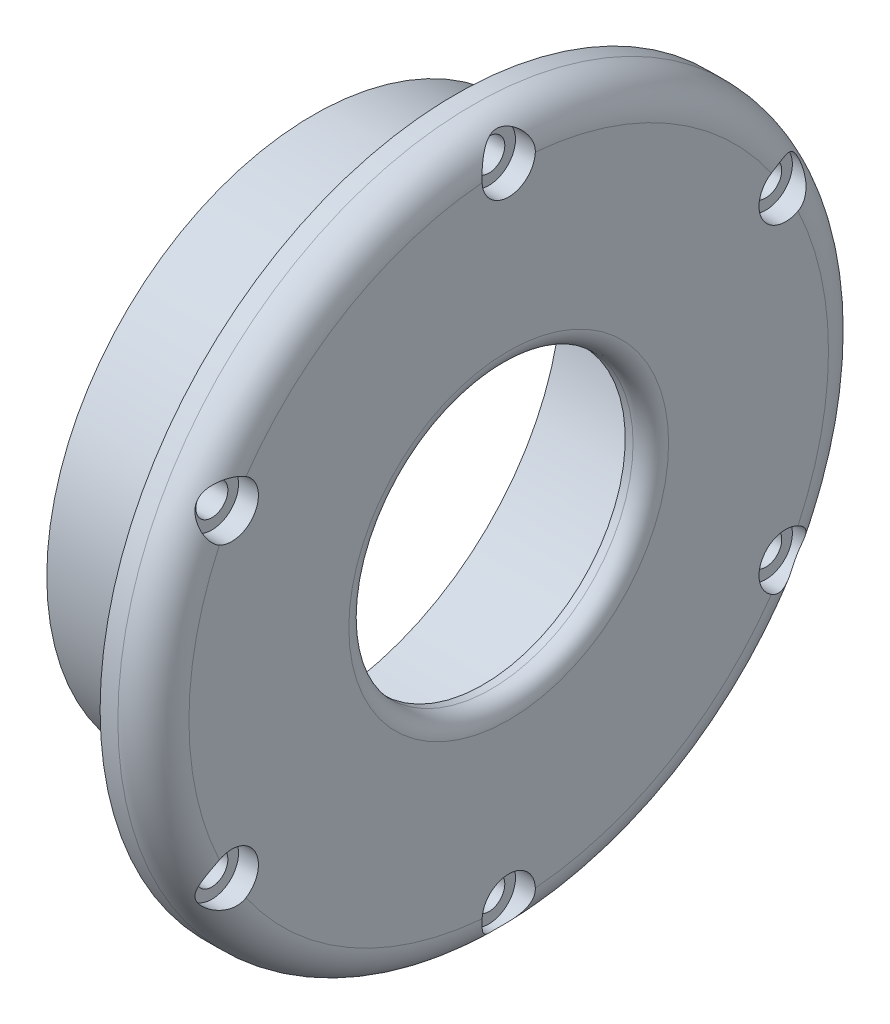
SolidWorks part; units mm, degrees
ref_plane "Front Plane" through (0, 0, 0) normal (0, 0, 1) x (1, 0, 0)
ref_plane "Top Plane" through (0, 0, 0) normal (0, 1, 0) x (1, 0, 0)
ref_plane "Right Plane" through (0, 0, 0) normal (1, 0, 0) x (0, 0, -1)
sketch "Sketch1" plane through (0, 0, 0) normal (0, 0, 1) x (1, 0, 0)
  line L0 (-15.2619, -32.7558) -> (53.5176, -32.7558)
  line L1 (22.9739, 67.2442) -> (37.9739, 67.2442)
  line L2 (-17.0261, 42.2442) -> (-17.0261, 37.2442)
  line L3 (30.7757, 7.2442) -> (37.9739, 7.2442)
  line L5 (37.9739, 67.2442) -> (37.9739, 7.2442)
  line L16 (-17.0261, 42.2442) -> (22.9739, 42.2442)
  line L17 (22.9739, 67.2442) -> (22.9739, 42.2442)
  line L20 (-17.0261, 37.2442) -> (17.9739, 37.2442)
  line L21 (17.9739, 31.2442) -> (17.9739, 37.2442)
  line L22 (17.9739, 31.2442) -> (22.9757, 31.2442)
  line L25 (30.7757, 22.2442) -> (30.7757, 7.2442)
  line L32 (30.7757, 22.2442) -> (22.9757, 22.2442)
  line L33 (22.9757, 31.2442) -> (22.9757, 22.2442)
  dimension "D1" = 60
  dimension "D2" = 40
  dimension "D3" = 40
  dimension "D4" = 35
  dimension "D5" = 6
  dimension "D6" = 5
  dimension "D7" = 15
  dimension "D8" = 7.1982
  dimension "D9" = 30
  dimension "D10" = 15
revolve "Revolve1" add sketch "Sketch1" angle 360 about L0 region at (25.1641, 40.2485, 0)
sketch "Sketch2" plane through (37.9739, 0, 0) normal (1, 0, 0) x (0, 0, -1)
  line L0 (0, -32.7558) -> (0, 57.2442)
  line L1 (0, -32.7558) -> (77.9423, 12.2442)
  line L2 (0, -32.7558) -> (77.9423, -77.7558)
  line L3 (0, -32.7558) -> (0, -122.7558)
  line L4 (0, -32.7558) -> (-77.9423, -77.7558)
  line L5 (0, -32.7558) -> (-77.9423, 12.2442)
  point P6 (0, 57.2442)
  point P9 (0, -32.7558)
  point P24 (-77.9423, 12.2442)
  point P27 (-77.9423, -77.7558)
  point P30 (0, -122.7558)
  point P33 (77.9423, -77.7558)
  point P36 (77.9423, 12.2442)
  dimension "D1" = 90
  dimension "D2" = 6
hole_wizard "CBORE for M8 Hex Socket Thin Head Cap Screw1" positions "Sketch2" profile "Sketch3" counterbore size "M8" standard "DIN"
sketch "Sketch3" plane through (37.9739, 12.2442, -77.9423) normal (0, 1, 0) x (0, 0, -1)
  line L0 (0, 0) -> (0, 17.7039)
  line L1 (0, 17.7039) -> (4.5, 15)
  line L2 (4.5, 15) -> (4.5, 5.6)
  line L3 (4.5, 5.6) -> (7.5, 5.6)
  line L4 (7.5, 5.6) -> (7.5, 0)
  line L5 (7.5, 0) -> (0, 0)
  line L10 (0, 17.7039) -> (-4.5, 15) construction
  line L11 (0, -6.35) -> (0, 107.95) construction
  dimension "Hole Dia." = 9
  dimension "Hole Depth" = 15
  dimension "C'Bore Dia." = 15
  dimension "C'Bore Depth" = 5.6
  dimension "Drill Angle" = 118
fillet "Fillet1" radius 10 1 edges at (37.9739, -32.7558, 100)
fillet "Fillet2" radius 5 1 edges at (37.9739, -32.7558, 40)
